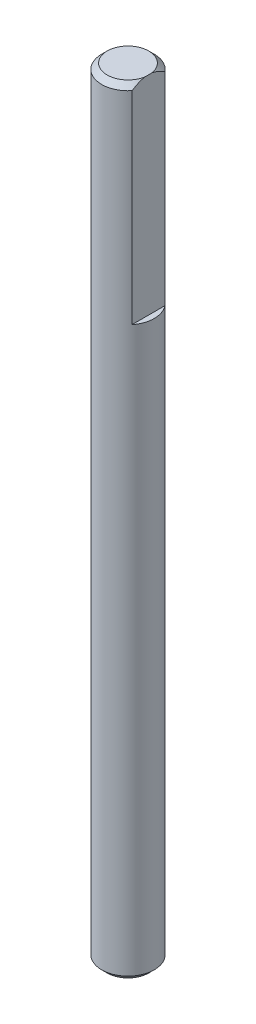
SolidWorks part; units mm, degrees
ref_plane "Front Plane" through (0, 0, 0) normal (0, 0, 1) x (1, 0, 0)
ref_plane "Top Plane" through (0, 0, 0) normal (0, 1, 0) x (1, 0, 0)
ref_plane "Right Plane" through (0, 0, 0) normal (1, 0, 0) x (0, 0, -1)
sketch "Sketch1" plane through (0, 0, 0) normal (0, 1, 0) x (1, 0, 0)
  circle A0 centre (0, 0) radius 2.4
  dimension "D1" = 4.8
extrude "Boss-Extrude1" add sketch "Sketch1" along normal blind 71
sketch "Sketch2" plane through (0, 71, 0) normal (0, 1, 0) x (1, 0, 0)
  line L0 (1.8735, 1.5) -> (1.8735, -1.5)
  arc A0 (1.8735, 1.5) -> (1.8735, -1.5) centre (0, 0) ccw construction
  circle A1 centre (0, 0) radius 2.4
  arc A2 (1.8735, -1.5) -> (1.8735, 1.5) centre (0, 0) ccw
  dimension "D2" = 3
  dimension "D1" = 0
extrude "Cut-Extrude1" cut sketch "Sketch2" against normal blind 19
chamfer "Chamfer1" distance 0.5 angle 45 2 edges at (0, 0, 2.4) (-2.4, 71, 0)
ref_axis "Axis1" through (0, 70.5, 0) along (0, -1, 0)
